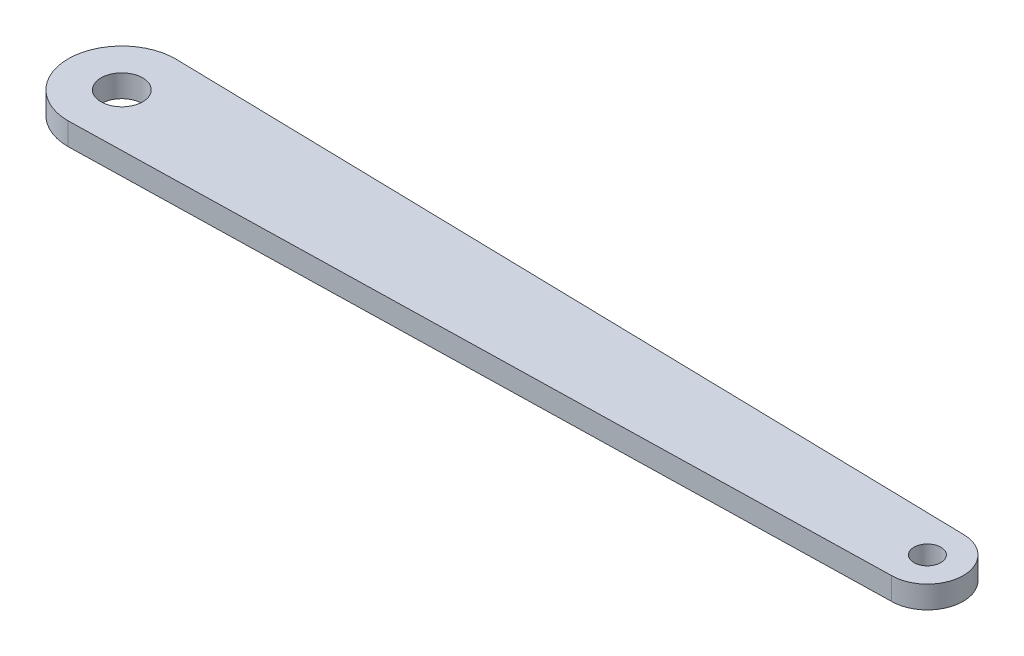
SolidWorks part; units mm, degrees
ref_plane "Front Plane" through (0, 0, 0) normal (0, 0, 1) x (1, 0, 0)
ref_plane "Top Plane" through (0, 0, 0) normal (0, 1, 0) x (1, 0, 0)
ref_plane "Right Plane" through (0, 0, 0) normal (1, 0, 0) x (0, 0, -1)
sketch "Sketch1" plane through (0, 0, 0) normal (0, 1, 0) x (1, 0, 0)
  line L0 (0, 0) -> (180, 0) construction
  line L1 (180.1778, 7.998) -> (0.2667, 11.997)
  line L2 (0, -12) -> (180, -8)
  circle A0 centre (0, 0) radius 4.65
  arc A1 (0.2667, 11.997) -> (0.5331, -11.9882) centre (0, 0) ccw
  arc A2 (180, -8) -> (180.1778, 7.998) centre (180, 0) ccw
  dimension "D1" = 9.3
  dimension "D2" = 12
  dimension "D3" = 8
  dimension "D4" = 180
extrude "Boss-Extrude1" add sketch "Sketch1" along normal blind 5 contours L2 A2 L1 A1 A0 region at (82.8459, 0, -0.0012)
sketch "Sketch2" plane through (0, 5, 0) normal (0, 1, 0) x (1, 0, 0)
  circle A0 centre (180, 0) radius 3
  dimension "D1" = 6
extrude "Cut-Extrude1" cut sketch "Sketch2" against normal through all contours A0
